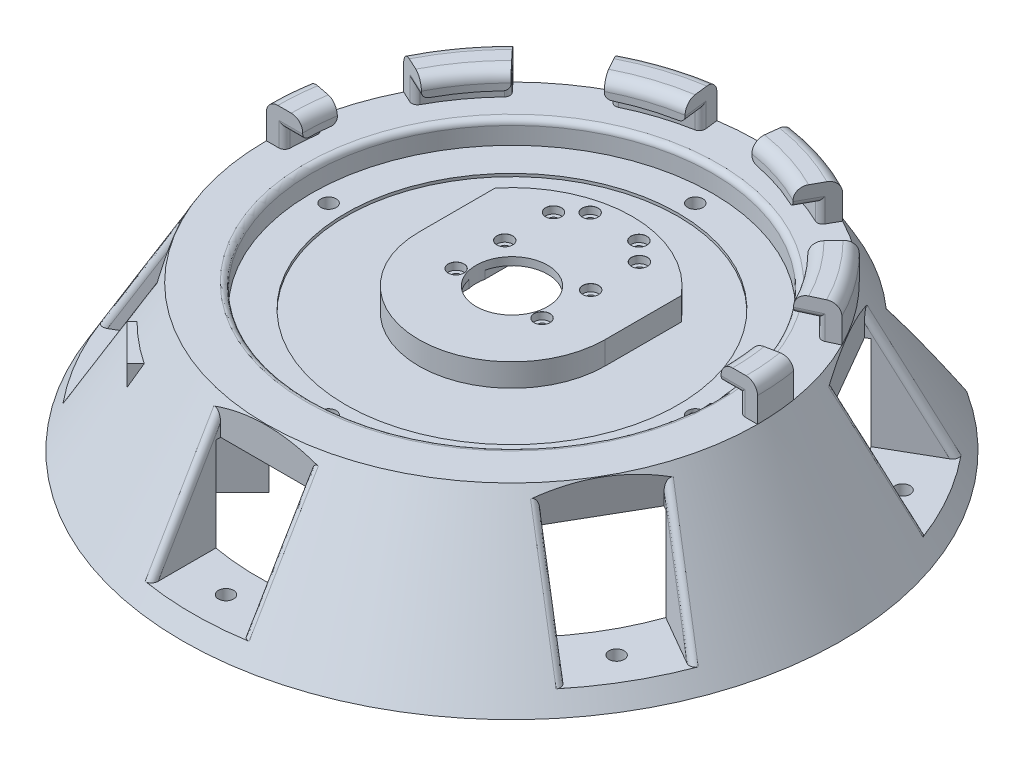
SolidWorks part; units mm, degrees
note: The reader was unsure of these and kept them because the rebuilt part matched: shared geometry of "Sketch3<3>".
material "PLA"
ref_plane "Front Plane" through (0, 0, 0) normal (0, 0, 1) x (1, 0, 0)
ref_plane "Top Plane" through (0, 0, 0) normal (0, 1, 0) x (1, 0, 0)
ref_plane "Right Plane" through (0, 0, 0) normal (1, 0, 0) x (0, 0, -1)
sketch "Sketch1" plane through (0, 0, 0) normal (0, 0, 1) x (1, 0, 0)
  line L0 (0, 0) -> (-85.725, 0)
  line L1 (-85.725, 0) -> (-115.0544, -50.8)
  line L2 (-115.0544, -50.8) -> (0, -50.8)
  line L6 (0, 0) -> (0, -50.8) construction
  line L7 (0, 0) -> (0, -50.8)
  dimension "D1" = 85.725
  dimension "D2" = 115.0544
  dimension "D3" = 50.8
revolve "Revolve1" add sketch "Sketch1" angle 360 about L6
sketch "Sketch2" plane through (0, 0, 0) normal (0, 1, 0) x (1, 0, 0)
  circle A0 centre (0, 0) radius 12.5
  dimension "D1" = 25
extrude "Cut-Extrude1" cut sketch "Sketch2" against normal through all
sketch "Sketch3" plane through (0, 0, 0) normal (0, 1, 0) x (1, 0, 0)
  line L0 (-32.5, 0) -> (-32.5, 26.6036)
  line L1 (-32.5, 26.6036) -> (32.5, 26.6036)
  line L2 (32.5, 26.6036) -> (32.5, 0)
  circle A0 centre (0, 0) radius 32.5
  circle A1 centre (0, 0) radius 70
  circle A2 centre (0, 0) radius 42
  circle M1 centre (0, 0) radius 12.5
  dimension "D1" = 65
  dimension "D2" = 140
  dimension "D3" = 84
extrude "Cut-Extrude2" cut sketch "Sketch3" against normal blind 8 contours A1 A0 L0 L1 L2 | A1 A2
sketch "Sketch7" plane through (0, -50.8, 0) normal (0, -1, 0) x (1, 0, 0)
  line L0 (0, 88.9) -> (0, -161.1) construction
  line L1 (-85.4, 0) -> (85.4, 0) construction
  line L2 (-60, -65.5989) -> (-60, -161.1)
  line L3 (-60, -161.1) -> (60, -161.1)
  line L4 (60, -161.1) -> (60, -65.5989)
  line L5 (-60, -65.5989) -> (60, -65.5989) construction
  arc A2 (60, -65.5989) -> (-60, -65.5989) centre (0, 0) ccw
  dimension "D1" = 177.8
  dimension "D2" = 25.4
  dimension "D3" = 25.4
  dimension "D4" = 120
  dimension "D5" = 250
extrude "Cut-Extrude5" cut sketch "Sketch7" against normal blind 39 contours L3 L4 A2 L2
sketch "Sketch8" plane through (0, 0, 0) normal (0, 1, 0) x (1, 0, 0)
  line L0 (0, 0) -> (0, -115.0544) construction
  line L2 (-15.875, -123.925) -> (15.875, -123.925)
  line L3 (-15.875, -123.925) -> (-15.875, -85.825)
  line L4 (-15.875, -85.825) -> (15.875, -85.825)
  line L5 (15.875, -123.925) -> (15.875, -85.825)
  line L6 (-15.875, -123.925) -> (15.875, -85.825) construction
  line L7 (-15.875, -85.825) -> (15.875, -123.925) construction
  arc A0 (-60, 98.1708) -> (60, 98.1708) centre (0, 0) ccw construction
  point P6 (0, -104.875)
  dimension "D1" = 85.825
  dimension "D2" = 38.1
  dimension "D3" = 31.75
extrude "Cut-Extrude6" cut sketch "Sketch8" against normal blind 44.45
pattern_circular "CirPattern2" count 6 over 360 about axis through (0, 0, 0) along (0, 1, 0) of "Cut-Extrude6"
sketch "Sketch9" plane through (0, 0, 0) normal (0, 1, 0) x (1, 0, 0)
  line L0 (0, 0) -> (0, -115.0544) construction
  arc A0 (-60, 98.1708) -> (60, 98.1708) centre (0, 0) ccw construction
  circle A1 centre (0, -99.8144) radius 2.65
  dimension "D1" = 5.3
  dimension "D2" = 15.24
extrude "Cut-Extrude7" cut sketch "Sketch9" against normal through all
pattern_circular "CirPattern3" count 6 over 360 about axis through (0, 0, 0) along (0, 1, 0) of "Cut-Extrude7"
sketch "Sketch12" plane through (0, 0, 0) normal (0, 0, 1) x (1, 0, 0)
  line L0 (85.725, 0) -> (85.725, 12.7)
  line L1 (85.725, 12.7) -> (73.025, 12.7)
  line L2 (73.025, 12.7) -> (73.025, 6.35)
  line L3 (73.025, 6.35) -> (79.375, 6.35)
  line L4 (79.375, 6.35) -> (79.375, 0)
  line L5 (85.725, 0) -> (-85.725, 0) construction
  line L6 (0, 0) -> (0, 12.7) construction
  line L7 (12.5, 0) -> (-12.5, 0) construction
  line L8 (79.375, 0) -> (85.725, 0)
  point P13 (0, 6.35)
  dimension "D1" = 6.35
  dimension "D2" = 73.025
  dimension "D3" = 79.375
  dimension "D4" = 12.7
  dimension "D5" = 12.7
revolve "Revolve2" add sketch "Sketch12" angle 180 about L6
sketch "Sketch15" plane through (0, -11.8, 0) normal (0, -1, 0) x (1, 0, 0)
  line L0 (0, -1000) -> (0, 49000) construction
  point P1 (-15, 4.5)
  point P4 (-15, -12.5)
  point P5 (-15, -29.5)
  point P6 (-8.5, -35.8)
  point P7 (8.5, -35.8)
  point P8 (15, -29.5)
  point P9 (15, -12.5)
  point P10 (15, 4.5)
  dimension "D1" = 17
  dimension "D2" = 17
  dimension "D3" = 4.5
  dimension "D4" = 15
  dimension "D5" = 8.5
  dimension "D6" = 35.8
sketch "Sketch18" plane through (0, 12.7, 0) normal (0, 1, 0) x (1, 0, 0)
  line L0 (46.6433, 89.7185) -> (70.9138, 72.0849)
  line L1 (0, 201000) -> (0, -249000) construction
  line L2 (-15, 100) -> (-9, 50)
  line L3 (-9, 50) -> (9, 50)
  line L4 (9, 50) -> (15, 100)
  line L5 (-15, 100) -> (15, 100)
  line L6 (36.6704, 35.1608) -> (70.9138, 72.0849)
  line L7 (22.1081, 45.7409) -> (36.6704, 35.1608)
  line L8 (46.6433, 89.7185) -> (22.1081, 45.7409)
  line L9 (90.4704, 45.1675) -> (99.7409, 16.6359)
  line L10 (50.334, 6.8913) -> (99.7409, 16.6359)
  line L11 (44.7717, 24.0104) -> (50.334, 6.8913)
  line L12 (90.4704, 45.1675) -> (44.7717, 24.0104)
  line L13 (99.7409, -16.6359) -> (90.4704, -45.1675)
  line L14 (44.7717, -24.0104) -> (90.4704, -45.1675)
  line L15 (50.334, -6.8913) -> (44.7717, -24.0104)
  line L16 (99.7409, -16.6359) -> (50.334, -6.8913)
  line L17 (70.9138, -72.0849) -> (46.6433, -89.7185)
  line L18 (22.1081, -45.7409) -> (46.6433, -89.7185)
  line L19 (36.6704, -35.1608) -> (22.1081, -45.7409)
  line L20 (70.9138, -72.0849) -> (36.6704, -35.1608)
  line L21 (15, -100) -> (-15, -100)
  line L22 (-9, -50) -> (-15, -100)
  line L23 (9, -50) -> (-9, -50)
  line L24 (15, -100) -> (9, -50)
  line L25 (-46.6433, -89.7185) -> (-70.9138, -72.0849)
  line L26 (-36.6704, -35.1608) -> (-70.9138, -72.0849)
  line L27 (-22.1081, -45.7409) -> (-36.6704, -35.1608)
  line L28 (-46.6433, -89.7185) -> (-22.1081, -45.7409)
  line L29 (-90.4704, -45.1675) -> (-99.7409, -16.6359)
  line L30 (-50.334, -6.8913) -> (-99.7409, -16.6359)
  line L31 (-44.7717, -24.0104) -> (-50.334, -6.8913)
  line L32 (-90.4704, -45.1675) -> (-44.7717, -24.0104)
  line L33 (-99.7409, 16.6359) -> (-90.4704, 45.1675)
  line L34 (-44.7717, 24.0104) -> (-90.4704, 45.1675)
  line L35 (-50.334, 6.8913) -> (-44.7717, 24.0104)
  line L36 (-99.7409, 16.6359) -> (-50.334, 6.8913)
  line L37 (-70.9138, 72.0849) -> (-46.6433, 89.7185)
  line L38 (-22.1081, 45.7409) -> (-46.6433, 89.7185)
  line L39 (-36.6704, 35.1608) -> (-22.1081, 45.7409)
  line L40 (-70.9138, 72.0849) -> (-36.6704, 35.1608)
  point P4 (0, 50)
  point P7 (0, 100)
  point P48 (0, 0)
  dimension "D1" = 18
  dimension "D2" = 50
  dimension "D3" = 30
  dimension "D4" = 50
  dimension "D5" = 10
extrude "Cut-Extrude9" cut sketch "Sketch18" against normal blind 12.7
sketch "Sketch20" plane through (0, -11.8, 0) normal (0, -1, 0) x (1, 0, 0)
  line L0 (-22.5, -33) -> (-12.5, -40)
  line L1 (22.5, 23) -> (-22.5, 23)
  line L2 (22.5, 23) -> (22.5, -40)
  line L3 (22.5, -40) -> (-22.5, -40)
  line L4 (-22.5, 23) -> (-22.5, -40)
  line L7 (-12.5, -40) -> (12.5, -40)
  line L8 (12.5, -40) -> (22.5, -33)
  point P0 (0, -10)
  dimension "D1" = 23
  dimension "D2" = 45
  dimension "D3" = 10
  dimension "D4" = 10
  dimension "D5" = 7
  dimension "D6" = 7
  dimension "D7" = 10
  dimension "D8" = 40
  dimension "D9" = 22.5
extrude "Cut-Extrude11" cut sketch "Sketch3<3>" against normal blind 1 contours A0 L1 M1 | A0 L1 L0 | L1 A0 | L1 A2 A0 | A0 L2 L1
sketch "Sketch3<3>" plane through (0, 0, 0) normal (0, 1, 0) x (1, 0, 0) same geometry as "Sketch3"
sketch "Sketch22" plane through (0, -1, 0) normal (0, 1, 0) x (1, 0, 0)
  circle A0 centre (-15, 12.5) radius 1.4
  circle A1 centre (-15, 29.5) radius 1.4
  circle A2 centre (-8.5, 35.8) radius 1.4
  circle A3 centre (8.5, 35.8) radius 1.4
  circle A4 centre (15, 29.5) radius 1.4
  circle A5 centre (15, 12.5) radius 1.4
  circle A6 centre (15, -4.5) radius 1.4
  circle A7 centre (-15, -4.5) radius 1.4
  dimension "D1" = 17
  dimension "D2" = 17
  dimension "D3" = 2.8
  dimension "D4" = 2.8
  dimension "D5" = 2.8
  dimension "D6" = 2.8
  dimension "D7" = 2.8
  dimension "D8" = 2.8
  dimension "D9" = 2.8
  dimension "D10" = 2.8
  dimension "D11" = 17
  dimension "D12" = 30
  dimension "D13" = 30
  dimension "D14" = 30
  dimension "D15" = 17
  dimension "D16" = 17
  dimension "D17" = 6.3
  dimension "D18" = 6.3
  dimension "D19" = 35.8
  dimension "D20" = 8.5
  dimension "D21" = 35.8
  dimension "D22" = 15
  dimension "D23" = 19.5256
  dimension "D24" = 15.6605
hole_wizard "CBORE for M2.5 SHCS1" positions "Sketch23" profile "Sketch24" counterbore size "M2.5" standard "ANSI Metric" end condition through all
sketch "Sketch23" plane through (0, -1, 0) normal (0, 1, 0) x (1, 0, 0)
  point P0 (-15, -4.5)
  point P3 (-15, 12.5)
  point P6 (-15, 29.5)
  point P9 (-8.5, 35.8)
  point P12 (8.5, 35.8)
  point P15 (15, 29.5)
  point P18 (15, 12.5)
  point P21 (15, -4.5)
sketch "Sketch24" plane through (-15, -1, 4.5) normal (1, 0, 0) x (0, 0, 1)
  line L0 (0, 0) -> (0, 49.8)
  line L1 (0, 49.8) -> (1.45, 49.8)
  line L3 (1.45, 49.8) -> (1.45, 2.5)
  line L4 (2.75, 2.5) -> (1.45, 2.5)
  line L5 (2.75, 2.5) -> (2.75, 0.025)
  line L6 (2.75, 0.025) -> (2.775, 0)
  line L7 (2.775, 0) -> (0, 0)
  line L8 (-2.75, 0.025) -> (-2.775, 0) construction
  line L11 (0, -6.35) -> (0, 107.95) construction
  dimension "Thru Hole Dia." = 2.9
  dimension "Thru Hole Depth" = 49.8
  dimension "C'Bore Dia." = 5.5
  dimension "C'Bore Depth" = 2.5
  dimension "Near C'Sink Dia." = 5.55
  dimension "Near C'Sink Angle" = 90
fillet "Fillet1" radius 4 12 edges at (85.4509, 12.7, -6.8497) (69.353, 12.7, -50.3879) (26.4905, 12.7, -81.5293) (-26.4905, 12.7, -81.5293) (-69.353, 12.7, -50.3879) (-85.4509, 12.7, -6.8497) (-72.8088, 12.7, -5.6148) (-59.0785, 12.7, -42.923) (-22.566, 12.7, -69.4509) (22.566, 12.7, -69.4509) (59.0785, 12.7, -42.923) (72.8088, 12.7, -5.6148)
fillet "Fillet2" radius 2 12 edges at (75.2789, 6.35, -11.8112) (76.2, 6.35, 0) (53.9595, 6.35, -53.8033) (67.8444, 6.35, -34.6924) (12.0293, 6.35, -75.2444) (34.4956, 6.35, -67.9447) (-12.0293, 6.35, -75.2444) (-34.4956, 6.35, -67.9447) (-53.9595, 6.35, -53.8033) (-67.8444, 6.35, -34.6924) (-75.2789, 6.35, -11.8112) (-76.2, 6.35, 0)
fillet "Fillet3" radius 2 12 edges at (-78.3963, 4.175, -12.4261) (-56.1201, 4.175, -56.1331) (-70.7278, 4.175, -36.0273) (-12.4079, 4.175, -78.3992) (56.1201, 4.175, -56.1331) (78.3963, 4.175, -12.4261) (-79.375, 4.175, 0) (-36.0437, 4.175, -70.7195) (12.4079, 4.175, -78.3992) (36.0437, 4.175, -70.7195) (70.7278, 4.175, -36.0273) (79.375, 4.175, 0)
fillet "Fillet4" radius 2 10 edges
fillet "Fillet5" radius 2 1 edges at (0, 0, 70)
fillet "Fillet9" radius 1 2 edges
sketch "Sketch28" plane through (0, -11.8, 0) normal (0, -1, 0) x (1, 0, 0)
  line L0 (9.2, 12) -> (-9.2, 12)
  line L1 (-12.2, 9) -> (-12.2, -30)
  line L2 (-9.2, -33) -> (9.2, -33)
  line L3 (12.2, -30) -> (12.2, 9)
  arc A0 (-9.2, 12) -> (-12.2, 9) centre (-9.2, 9) ccw
  arc A1 (-12.2, -30) -> (-9.2, -33) centre (-9.2, -30) ccw
  arc A2 (9.2, -33) -> (12.2, -30) centre (9.2, -30) ccw
  arc A3 (12.2, 9) -> (9.2, 12) centre (9.2, 9) ccw
extrude "Cut-Extrude12" cut sketch "Sketch28" against normal offset from surface (8.05 mm away) 2.75
extrude "Cut-Extrude15" cut sketch "Sketch20" against normal offset from surface (5.3 mm away) 2.75
sketch "Sketch29" plane through (0, -8, 0) normal (0, 1, 0) x (1, 0, 0)
  point P0 (0, 64)
  point P5 (64, 0)
  point P6 (0, -64)
  point P7 (-64, 0)
  point P8 (0, 0)
  dimension "D1" = 64
  dimension "D2" = 4
hole_wizard "M5 Clearance Hole1" positions "Sketch32" profile "Sketch33" hole size "M5" standard "ANSI Metric" end condition up to next
sketch "Sketch32" plane through (0, -8, 0) normal (0, 1, 0) x (1, 0, 0)
  point P0 (0, 64)
  point P3 (64, 0)
  point P6 (0, -64)
  point P9 (-64, 0)
sketch "Sketch33" plane through (0, -8, -64) normal (1, 0, 0) x (0, 0, 1)
  line L0 (0, 0) -> (0, 3.8)
  line L1 (0, 3.8) -> (2.65, 3.8)
  line L2 (2.65, 3.8) -> (2.65, 0)
  line L5 (2.65, 0) -> (0, 0)
  line L11 (0, -6.35) -> (0, 107.95) construction
  dimension "Thru Hole Dia." = 5.3
  dimension "Thru Hole Depth" = 3.8
sketch "Sketch34" plane through (0, -8, 0) normal (0, 1, 0) x (1, 0, 0)
  circle A0 centre (0, 0) radius 70
  circle A1 centre (0, 0) radius 58
  line M5 (-32.5, 0) -> (-32.5, 26.6036)
  arc M6 (-32.5, 26.6036) -> (32.5, 26.6036) centre (0, 0) cw
  line M7 (32.5, 26.6036) -> (32.5, 0)
  arc M8 (32.5, 0) -> (-32.5, 0) centre (0, 0) cw
  dimension "D1" = 140
  dimension "D2" = 116
extrude "Cut-Extrude16" cut sketch "Sketch34" against normal blind 1 contours A1 M8 M5 M6 M7
sketch "Sketch37" plane through (0, 0, 0) normal (0, 1, 0) x (1, 0, 0)
  circle A0 centre (0, 0) radius 111.3882
  dimension "D1" = 222.7764
sketch "Sketch39" plane through (0, -50.8, 0) normal (0, -1, 0) x (1, 0, 0)
  line L0 (-67.1751, 67.1751) -> (-42.4264, 42.4264)
  line L1 (-72, 12.5) -> (-107, 12.5)
  line L2 (-72, 12.5) -> (-72, -12.5)
  line L3 (-72, -12.5) -> (-107, -12.5)
  line L4 (-107, 12.5) -> (-107, -12.5)
  line L5 (-72, 0) -> (0, 0) construction
  line L6 (0, 0) -> (72, 0) construction
  line L7 (107, 12.5) -> (72, 12.5)
  line L8 (107, 12.5) -> (107, -12.5)
  line L9 (107, -12.5) -> (72, -12.5)
  line L10 (72, 12.5) -> (72, -12.5)
  line L13 (-42.4264, 42.4264) -> (-29.6985, 55.1543)
  line L14 (-29.6985, 55.1543) -> (-54.4472, 79.9031)
  line L15 (-54.4472, 79.9031) -> (-67.1751, 67.1751)
  line L16 (54.4472, 79.9031) -> (29.6985, 55.1543)
  line L17 (29.6985, 55.1543) -> (42.4264, 42.4264)
  line L18 (42.4264, 42.4264) -> (67.1751, 67.1751)
  line L19 (67.1751, 67.1751) -> (54.4472, 79.9031)
  line L21 (0, 0) -> (101.0152, 101.0152) construction
  line L22 (0, 0) -> (-104.6054, 104.6054) construction
  arc M26 (-60, -65.5989) -> (60, -65.5989) centre (0, 0) cw
  dimension "D1" = 25
  dimension "D2" = 35
  dimension "D3" = 35
  dimension "D4" = 35
  dimension "D5" = 72
  dimension "D6" = 72
  dimension "D7" = 60
  dimension "D8" = 60
  dimension "D9" = 18
  dimension "D10" = 18
  dimension "D11" = 35
extrude "Boss-Extrude1" add sketch "Sketch39" along a picked direction on the side against the normal blind 39 contours L17 L18 L16 M26 | L7 L10 L9 M26 | L3 L2 L1 M26 | L0 L13 L14 L15
fillet "Fillet10" radius 10 2 edges at (36.0624, -11.8, 48.7904) (-36.0624, -11.8, 48.7904)
